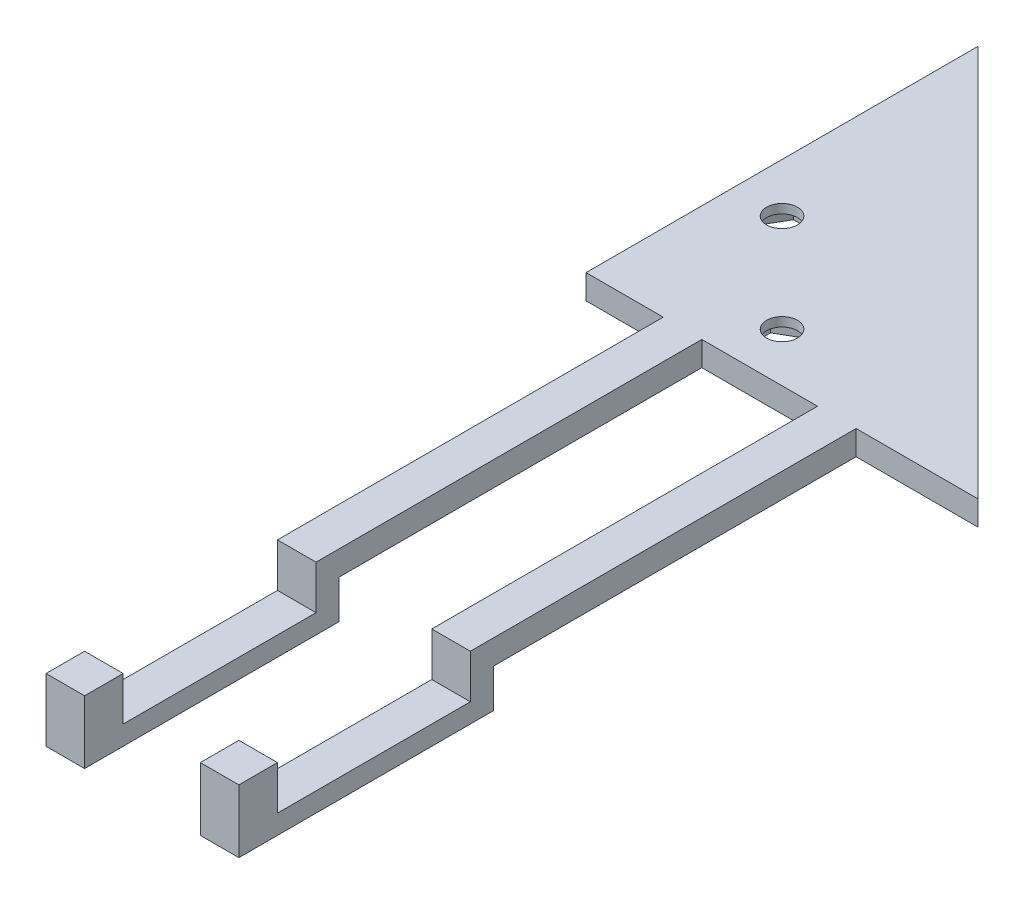
SolidWorks part; units mm, degrees
ref_plane "Front" through (0, 0, 0) normal (0, 0, 1) x (1, 0, 0)
ref_plane "Top" through (0, 0, 0) normal (0, 1, 0) x (1, 0, 0)
ref_plane "Right" through (0, 0, 0) normal (1, 0, 0) x (0, 0, -1)
sketch "Sketch1" plane through (0, 0, 0) normal (0, 1, 0) x (1, 0, 0)
  line L0 (0, 0) -> (50.8, 0)
  line L1 (-55, 0) -> (55, 0) construction
  line L2 (50.8, 0) -> (0, 50.8)
  line L3 (0, -55) -> (0, 55) construction
  line L4 (0, 50.8) -> (0, 0)
  dimension "D1" = 50.8
  dimension "D2" = 50.8
extrude "Boss-Extrude1" add sketch "Sketch1" along normal blind 3.175 contours L2 L4 L0
sketch "Sketch2" plane through (0, 3.175, 0) normal (0, 1, 0) x (1, 0, 0)
  line L0 (0, -55) -> (0, 55) construction
  line L1 (-55, 0) -> (55, 0) construction
  line L2 (0, 0) -> (25.4, 25.4) construction
  line L3 (50.8, 0) -> (0, 50.8) construction
  circle A0 centre (19.05, 6.35) radius 2
  circle A1 centre (6.35, 19.05) radius 2
  dimension "D1" = 4
  dimension "D3" = 6.35
  dimension "D2" = 19.05
extrude "Cut-Extrude1" cut sketch "Sketch2" against normal through all contours A0 | A1
sketch "Sketch3" plane through (0, 3.175, 0) normal (0, 1, 0) x (1, 0, 0)
  line L0 (0, 0) -> (25.4, 25.4) construction
  line L1 (8.3707, 15.55) -> (10.3914, 19.05)
  line L2 (10.3914, 19.05) -> (8.3707, 22.55)
  line L3 (0, 0) -> (50.8, 0)
  line L4 (50.8, 0) -> (0, 50.8)
  line L5 (0, 50.8) -> (0, 0)
  line L6 (0, 0) -> (50.8, 0)
  line L7 (50.8, 0) -> (0, 50.8)
  line L8 (0, 50.8) -> (0, 0)
  line L9 (8.3707, 22.55) -> (4.3293, 22.55)
  line L10 (4.3293, 22.55) -> (2.3086, 19.05)
  line L11 (2.3086, 19.05) -> (4.3293, 15.55)
  line L12 (4.3293, 15.55) -> (8.3707, 15.55)
  line L13 (22.55, 4.3293) -> (19.05, 2.3086)
  line L14 (19.05, 2.3086) -> (15.55, 4.3293)
  line L15 (15.55, 4.3293) -> (15.55, 8.3707)
  line L16 (15.55, 8.3707) -> (19.05, 10.3914)
  line L17 (19.05, 10.3914) -> (22.55, 8.3707)
  line L18 (22.55, 8.3707) -> (22.55, 4.3293)
  circle A0 centre (6.35, 19.05) radius 2 construction
  circle A1 centre (6.35, 19.05) radius 2
  circle A2 centre (19.05, 6.35) radius 2 construction
  circle A3 centre (19.05, 6.35) radius 2
  circle A4 centre (6.35, 19.05) radius 3.5 construction
  dimension "D2" = 7
  dimension "D1" = 0
extrude "Cut-Extrude2" cut sketch "Sketch3" along normal blind 2 from surface contours L2 L9 L10 L11 L12 L1 | L17 L18 L13 L14 L15 L16 starting at face at (6.35, 0, -21.05)
sketch "Sketch5" plane through (0, 0, 0) normal (1, 0, 0) x (0, 0, -1)
  line L0 (0, 3.1213) -> (0, -3.1213) construction
  line L1 (0, 3.175) -> (-50, 3.175)
  line L2 (0, 3.175) -> (0, 0)
  line L3 (0, 0) -> (-50, 0)
  line L4 (-50, 3.175) -> (-50, 0)
  line L5 (0, 3.175) -> (50.8, 3.175) construction
  line L6 (27.94, 0) -> (-27.94, 0) construction
  line L11 (-75, 0) -> (-80, 0)
  line L12 (-75, 0) -> (-75, 3.175)
  line L13 (-75, 3.175) -> (-80, 3.175)
  line L14 (-80, 0) -> (-80, 3.175)
  line L15 (-80, 0) -> (-47, 0)
  line L16 (-80, 0) -> (-80, -5)
  line L17 (-80, -5) -> (-47, -5)
  line L18 (-47, 0) -> (-47, -5)
  line L20 (-75, 0) -> (-50, 0)
  line L21 (-75, 0) -> (-75, -2.5)
  line L22 (-75, -2.5) -> (-50, -2.5)
  line L23 (-50, 0) -> (-50, -2.5)
  dimension "D1" = 3.175
  dimension "D2" = 30
  dimension "D3" = 5
  dimension "D4" = 50
  dimension "D5" = 3
  dimension "D6" = 5
  dimension "D7" = 2.5
extrude "Boss-Extrude2" add sketch "Sketch5" along normal blind 5 from offset 10 contours L14 L11 L12 L13 | L18 L3 L15 L11 L16 L17 | L1 L4 L3 L2 region at (0, 1.5875, 25) region at (0, -3.2622, 64.1098) region at (0, 1.5875, 77.5)
extrude "Boss-Extrude3" add sketch "Sketch5<3>" along normal blind 5 from offset 30 contours L18 L3 L15 L11 L16 L17 | L1 L4 L3 L2 | L13 L14 L11 L12 region at (0, 1.5875, 25) region at (0, -3.2622, 64.1098)
sketch "Sketch5<3>" plane through (0, 0, 0) normal (1, 0, 0) x (0, 0, -1) same geometry as "Sketch5"
